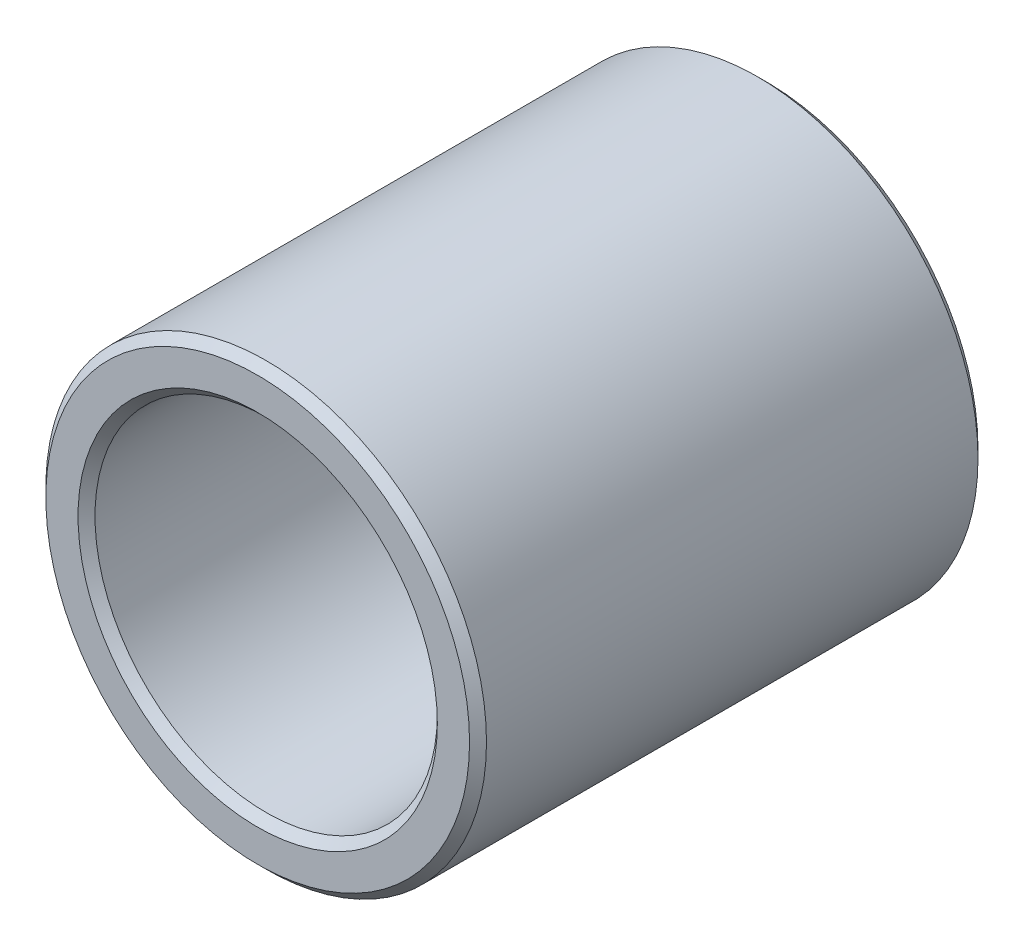
SolidWorks part; units mm, degrees
material "ABS"
ref_plane "Front Plane" through (0, 0, 0) normal (0, 0, 1) x (1, 0, 0)
ref_plane "Top Plane" through (0, 0, 0) normal (0, 1, 0) x (1, 0, 0)
ref_plane "Right Plane" through (0, 0, 0) normal (1, 0, 0) x (0, 0, -1)
sketch "Sketch1" plane through (0, 0, 0) normal (0, 0, 1) x (1, 0, 0)
  circle A0 centre (0, 0) radius 6.5
  circle A1 centre (0, 0) radius 5.05
  dimension "D1" = 10.1
  dimension "D2" = 13
extrude "Boss-Extrude1" add sketch "Sketch1" along normal blind 15
chamfer "Chamfer1" distance 0.25 angle 45 4 edges at (5.05, 0, 15) (6.5, 0, 15) (5.05, 0, 0) (6.5, 0, 0)
